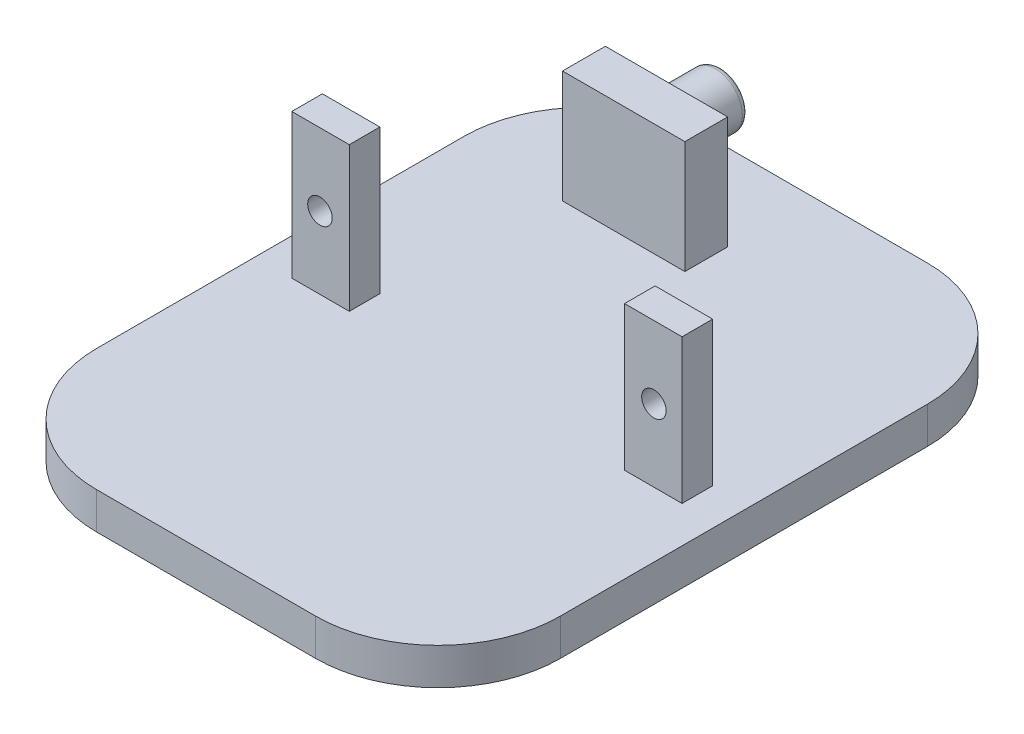
SolidWorks part; units mm, degrees
ref_plane "Plan de face" through (0, 0, 0) normal (0, 0, 1) x (1, 0, 0)
ref_plane "Plan de dessus" through (0, 0, 0) normal (0, 1, 0) x (1, 0, 0)
ref_plane "Plan de droite" through (0, 0, 0) normal (1, 0, 0) x (0, 0, -1)
sketch "Esquisse1" plane through (0, 0, 0) normal (0, 0, 1) x (1, 0, 0)
  line L1 (0, 0) -> (37.9, 0)
  line L2 (0, 0) -> (0, 3)
  line L3 (0, 3) -> (37.9, 3)
  line L4 (37.9, 0) -> (37.9, 3)
  dimension "D1" = 3
  dimension "D2" = 37.9
extrude "Boss.-Extru.1" add sketch "Esquisse1" along normal blind 50
sketch "Esquisse2" plane through (0, 3, 0) normal (0, 1, 0) x (1, 0, 0)
  line L0 (18.95, 0) -> (18.95, -50) construction
  line L1 (37.9, 0) -> (0, 0) construction
  line L2 (37.9, -50) -> (0, -50) construction
  line L3 (34.9, -50) -> (34.9, 0) construction
  line L4 (3, -50) -> (3, 0) construction
  line L5 (34.9, -25) -> (3, -25) construction
  line L7 (18.6, -10.52) -> (8.6, -10.52)
  line L12 (18.6, -10.52) -> (18.6, -7.02)
  line L13 (18.6, -7.02) -> (8.6, -7.02)
  line L14 (8.6, -10.52) -> (8.6, -7.02)
  dimension "D1" = 3
  dimension "D2" = 10.52
  dimension "D3" = 10
  dimension "D4" = 3.5
  dimension "D5" = 0.35
extrude "Boss.-Extru.2" add sketch "Esquisse2" along normal blind 9.2 contours L7 L14 L13 L12
sketch "Esquisse3" plane through (0, 0, 7.02) normal (0, 0, -1) x (-1, 0, 0)
  circle A0 centre (-13.6, 8.9) radius 2.2
  dimension "D1" = 4.4
extrude "Boss.-Extru.3" add sketch "Esquisse3" along normal up to surface (4.5 mm away)
fillet "Congé1" radius 0.5 1 edges at (13.6, 11.1, 2.52)
sketch "Esquisse5" plane through (0, 3, 0) normal (0, 1, 0) x (1, 0, 0)
  line L0 (18.95, -50) -> (18.95, 0) construction
  line L1 (30.2, -27.05) -> (34.9, -27.05)
  line L2 (30.2, -27.05) -> (30.2, -24.55)
  line L3 (30.2, -24.55) -> (34.9, -24.55)
  line L4 (34.9, -27.05) -> (34.9, -24.55)
  line L5 (37.9, -50) -> (0, -50) construction
  line L6 (37.9, 0) -> (0, 0) construction
  line L7 (7.7, -24.55) -> (3, -24.55)
  line L8 (3, -27.05) -> (3, -24.55)
  line L9 (7.7, -27.05) -> (3, -27.05)
  line L10 (7.7, -27.05) -> (7.7, -24.55)
  dimension "D1" = 4.7
  dimension "D2" = 2.5
extrude "Boss.-Extru.5" add sketch "Esquisse5" along normal up to surface (11.8 mm away) contours L7 L8 L9 L10 | L3 L4 L1 L2
sketch "Esquisse6" plane through (0, 0, 27.05) normal (0, 0, 1) x (1, 0, 0)
  circle A0 centre (32.6, 8.9) radius 1
  circle A1 centre (5.3, 8.9) radius 1
  dimension "D1" = 2
  dimension "D2" = 2
extrude "Enlèv. mat.-Extru.1" cut sketch "Esquisse6" against normal up to next
fillet "Congé2" radius 10 4 edges at (37.9, 1.5, 50) (37.9, 1.5, 0) (0, 1.5, 0) (0, 1.5, 50)
